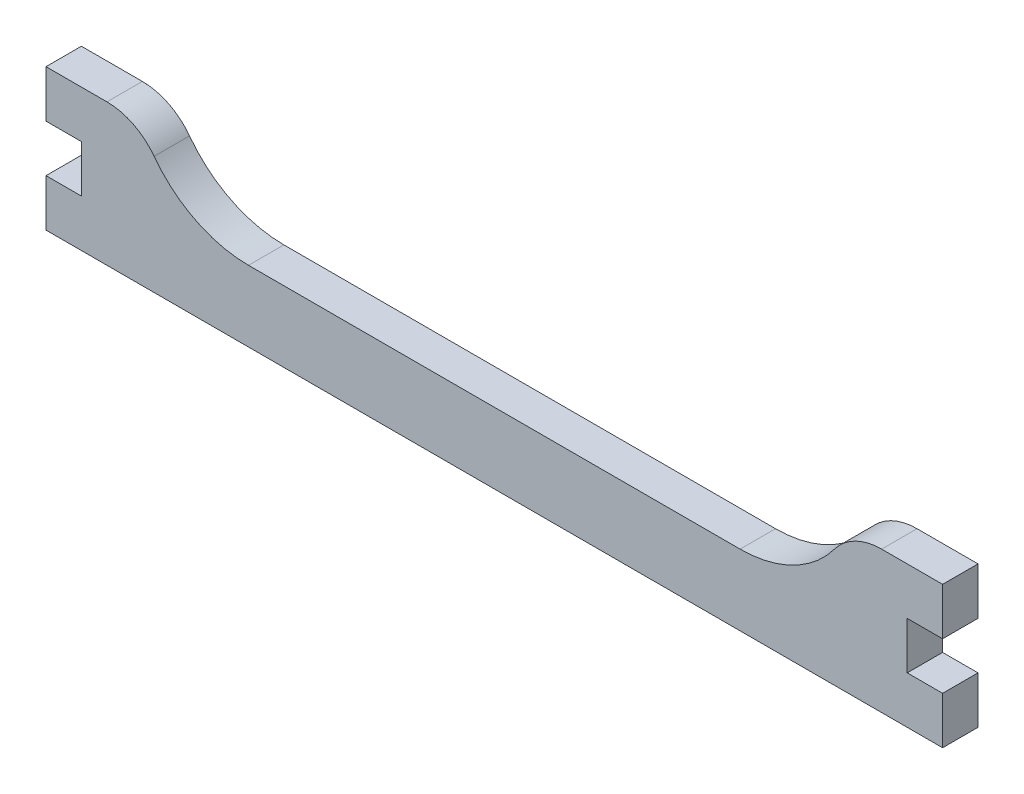
SolidWorks part; units mm, degrees
ref_plane "Front Plane" through (0, 0, 0) normal (0, 0, 1) x (1, 0, 0)
ref_plane "Top Plane" through (0, 0, 0) normal (0, 1, 0) x (1, 0, 0)
ref_plane "Right Plane" through (0, 0, 0) normal (1, 0, 0) x (0, 0, -1)
sketch "Sketch1" plane through (0, 0, 0) normal (0, 0, 1) x (1, 0, 0)
  line L1 (-35, 0) -> (35, 0)
  line L2 (-35, 0) -> (-35, 12)
  line L3 (-35, 12) -> (35, 12)
  line L4 (35, 0) -> (35, 12)
  point P4 (0, 0)
  dimension "D1" = 70
  dimension "D2" = 12
extrude "Boss-Extrude1" add sketch "Sketch1" along normal mid plane 3
sketch "Sketch2" plane through (0, 0, 1.5) normal (0, 0, 1) x (1, 0, 0)
  line L0 (-30, 12) -> (-30, 6)
  line L1 (35, 12) -> (-35, 12) construction
  line L2 (-30, 6) -> (30, 6)
  line L3 (30, 6) -> (30, 12)
  line L4 (-35, 0) -> (35, 0) construction
  point P8 (0, 6)
  line M7 (35, 12) -> (-35, 12)
  dimension "D1" = 6
  dimension "D2" = 60
extrude "Cut-Extrude1" cut sketch "Sketch2" against normal through all contours L2 L3 L0 M7 region at (0, 9, 1.5)
fillet "Fillet1" radius 10 2 edges at (30, 6, 0) (-30, 6, 0)
fillet "Fillet2" radius 5 2 edges at (30, 12, 0) (-30, 12, 0)
sketch "Sketch3" plane through (0, 0, 1.5) normal (0, 0, 1) x (1, 0, 0)
  line L0 (0, 0) -> (0, 6) construction
  line L1 (35, 12) -> (38, 12)
  line L2 (35, 12) -> (35, 8)
  line L3 (35, 8) -> (38, 8)
  line L4 (38, 12) -> (38, 8)
  line L5 (35, 0) -> (38, 0)
  line L6 (35, 0) -> (35, 4)
  line L7 (35, 4) -> (38, 4)
  line L8 (38, 0) -> (38, 4)
  line L9 (-20.8348, 6) -> (20.8348, 6) construction
  line L10 (-38, 0) -> (-38, 4)
  line L11 (-35, 4) -> (-38, 4)
  line L12 (-35, 0) -> (-35, 4)
  line L13 (-35, 0) -> (-38, 0)
  line L14 (-38, 12) -> (-38, 8)
  line L15 (-35, 8) -> (-38, 8)
  line L16 (-35, 12) -> (-35, 8)
  line L17 (-35, 12) -> (-38, 12)
  dimension "D1" = 4
  dimension "D2" = 4
  dimension "D3" = 3
extrude "Boss-Extrude2" add sketch "Sketch3" against normal up to vertex (3 mm away) up to point (-20.8348, 6, -1.5)
sketch "Sketch4" plane through (0, 0, 1.5) normal (0, 0, 1) x (1, 0, 0)
  line L0 (-38, 0) -> (38, 0) construction
  line L1 (25, 4) -> (32, 4)
  line L2 (25, 4) -> (25, 0)
  line L3 (25, 0) -> (32, 0)
  line L4 (32, 4) -> (32, 0)
  line L5 (25, 4) -> (32, 0) construction
  line L6 (25, 0) -> (32, 4) construction
  line L7 (35, 4) -> (35, 8) construction
  line L8 (0, 0) -> (0, 6) construction
  line L9 (-20.8348, 6) -> (20.8348, 6) construction
  line L10 (-25, 0) -> (-32, 4) construction
  line L11 (-25, 4) -> (-32, 0) construction
  line L12 (-32, 4) -> (-32, 0)
  line L13 (-25, 0) -> (-32, 0)
  line L14 (-25, 4) -> (-25, 0)
  line L15 (-25, 4) -> (-32, 4)
  point P0 (28.5, 2)
  point P17 (-28.5, 2)
  dimension "D1" = 7
  dimension "D2" = 4
  dimension "D3" = 3
extrude "Cut-Extrude2" [suppressed] cut sketch "Sketch4" against normal through all
